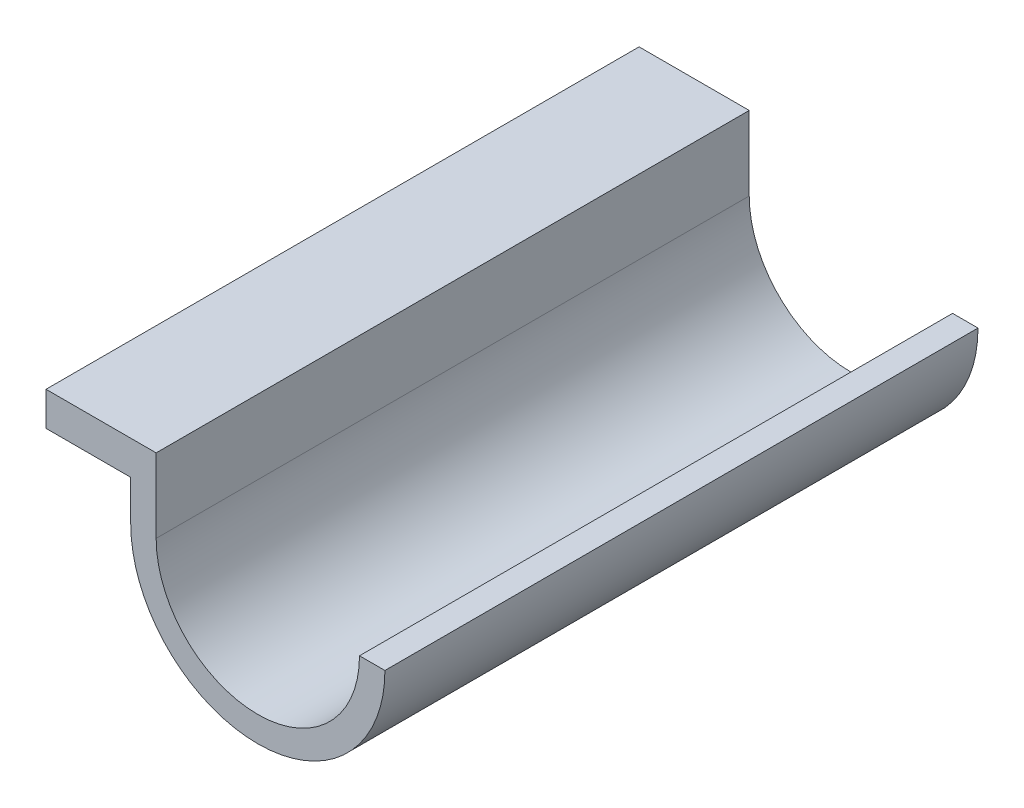
SolidWorks part; units mm, degrees
ref_plane "Front Plane" through (0, 0, 0) normal (0, 0, 1) x (1, 0, 0)
ref_plane "Top Plane" through (0, 0, 0) normal (0, 1, 0) x (1, 0, 0)
ref_plane "Right Plane" through (0, 0, 0) normal (1, 0, 0) x (0, 0, -1)
sketch "Sketch2" plane through (0, 0, 0) normal (0, 0, 1) x (1, 0, 0)
  circle A0 centre (0, 0) radius 15
  dimension "D1" = 30
extrude "Boss-Extrude1" add sketch "Sketch2" along normal blind 70 contours A0
sketch "Sketch3" plane through (0, 0, 70) normal (0, 0, 1) x (1, 0, 0)
  circle A0 centre (0, 0) radius 12
  dimension "D1" = 24
extrude "Cut-Extrude1" cut sketch "Sketch3" against normal through all
sketch "Sketch4" plane through (0, 0, 70) normal (0, 0, 1) x (1, 0, 0)
  line L1 (-16.0294, 0) -> (16.2012, 0)
  line L2 (-16.0294, 0) -> (-16.0294, 15.2787)
  line L3 (-16.0294, 15.2787) -> (16.2012, 15.2787)
  line L4 (16.2012, 0) -> (16.2012, 15.2787)
extrude "Cut-Extrude2" cut sketch "Sketch4" against normal through all
sketch "Sketch5" plane through (0, 0, 70) normal (0, 0, 1) x (1, 0, 0)
  line L0 (-15, 0) -> (-12, 0)
  line L1 (-12, 0) -> (-12, 8.7408)
  line L2 (-12, 8.7408) -> (-15, 8.7408)
  line L3 (-15, 8.7408) -> (-15, 0)
extrude "Boss-Extrude3" add sketch "Sketch5" against normal blind 70 contours L3 L0 L1 L2
sketch "Sketch6" plane through (-15, 0, 0) normal (-1, 0, 0) x (0, 0, 1)
  line L0 (0, 8.7408) -> (70, 8.7408)
  line L1 (70, 8.7408) -> (70, 4.7408)
  line L2 (70, 8.7408) -> (70, 0) construction
  line L3 (70, 4.7408) -> (0, 4.7408)
  line L4 (0, 8.7408) -> (0, 0) construction
  line L5 (0, 4.7408) -> (0, 8.7408)
  dimension "D1" = 4
extrude "Boss-Extrude4" add sketch "Sketch6" along normal blind 10
